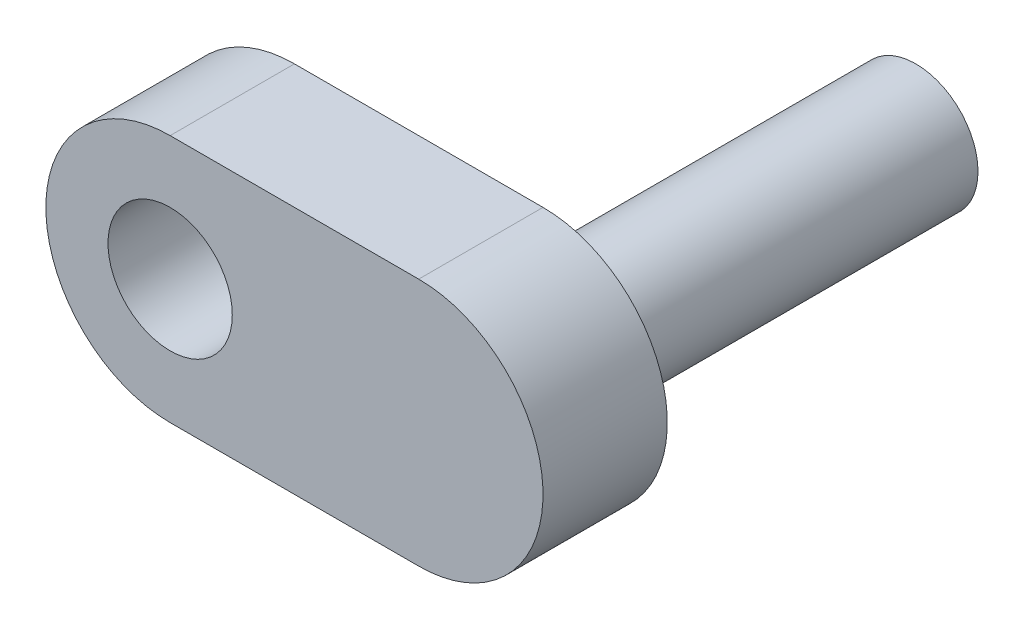
SolidWorks part; units mm, degrees
ref_plane "Front Plane" through (0, 0, 0) normal (0, 0, 1) x (1, 0, 0)
ref_plane "Top Plane" through (0, 0, 0) normal (0, 1, 0) x (1, 0, 0)
ref_plane "Right Plane" through (0, 0, 0) normal (1, 0, 0) x (0, 0, -1)
sketch "Sketch1" plane through (0, 0, 0) normal (0, 0, 1) x (1, 0, 0)
  line L0 (-13.9047, 0) -> (-3.9047, 0) construction
  line L1 (-13.9047, 5) -> (-3.9047, 5)
  line L2 (-13.9047, -5) -> (-3.9047, -5)
  arc A0 (-13.9047, 5) -> (-13.9047, -5) centre (-13.9047, 0) ccw
  arc A1 (-3.9047, -5) -> (-3.9047, 5) centre (-3.9047, 0) ccw
  circle A2 centre (-13.9047, 0) radius 2.5
  circle A3 centre (-3.9047, 0) radius 2.5
  point P3 (-8.9047, 0)
  dimension "D1" = 10
  dimension "D2" = 5
  dimension "D3" = 5
  dimension "D4" = 10
extrude "Boss-Extrude1" add sketch "Sketch1" along normal blind 5 contours L1 A1 L2 A0 | A2
extrude "Boss-Extrude2" add sketch "Sketch1<3>" against normal blind 15 contours A3
sketch "Sketch1<3>" plane through (0, 0, 0) normal (0, 0, 1) x (1, 0, 0) same geometry as "Sketch1"
